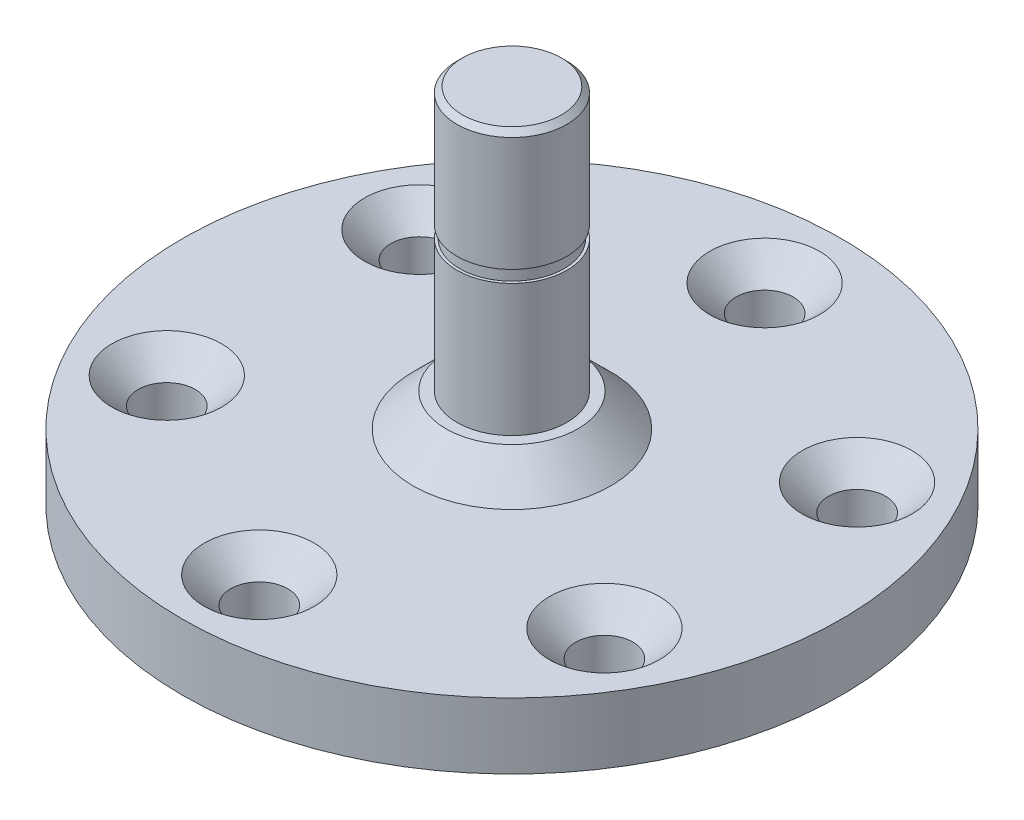
SolidWorks part; units mm, degrees
material "AISI 304"
ref_plane "前视基准面" through (0, 0, 0) normal (0, 0, 1) x (1, 0, 0)
ref_plane "上视基准面" through (0, 0, 0) normal (0, 1, 0) x (1, 0, 0)
ref_plane "右视基准面" through (0, 0, 0) normal (1, 0, 0) x (0, 0, -1)
sketch "草图1" plane through (0, 0, 0) normal (0, 1, 0) x (1, 0, 0)
  circle A0 centre (0, 0) radius 30
  dimension "D1" = 60
extrude "凸台-拉伸1" add sketch "草图1" along normal blind 6
sketch "草图2" plane through (0, 6, 0) normal (0, 1, 0) x (1, 0, 0)
  circle A0 centre (0, 0) radius 6
  dimension "D1" = 12
extrude "凸台-拉伸2" add sketch "草图2" along normal blind 3
sketch "草图3" plane through (0, 9, 0) normal (0, 1, 0) x (1, 0, 0)
  circle A0 centre (0, 0) radius 5
  dimension "D1" = 10
extrude "凸台-拉伸3" add sketch "草图3" along normal blind 24
sketch "草图4" plane through (0, 33, 0) normal (0, 1, 0) x (1, 0, 0)
  circle A0 centre (0, 0) radius 4.75
  dimension "D1" = 9.5
extrude "切除-拉伸1" cut sketch "草图4" along normal blind 1.1 from offset 12 flip side to cut offset against normal yes
sketch "草图5" plane through (0, 6, 0) normal (0, 1, 0) x (1, 0, 0)
  circle A0 centre (0, 0) radius 23 construction
  circle A1 centre (0, 23) radius 2.6
  circle A2 centre (19.9186, 11.5) radius 2.6
  circle A3 centre (19.9186, -11.5) radius 2.6
  circle A4 centre (0, -23) radius 2.6
  circle A5 centre (-19.9186, -11.5) radius 2.6
  circle A6 centre (-19.9186, 11.5) radius 2.6
  point P17 (0, 0)
  dimension "D1" = 46
  dimension "D2" = 5.2
  dimension "D3" = 6
extrude "切除-拉伸2" cut sketch "草图5" against normal through all
chamfer "倒角1" distance 3 angle 45 1 edges at (0, 6, 6)
chamfer "倒角2" distance 0.5 angle 45 1 edges at (0, 33, 5)
sketch "草图6" plane through (0, 0, 0) normal (0, -1, 0) x (1, 0, 0)
  circle A0 centre (0, 0) radius 13
  dimension "D1" = 26
extrude "切除-拉伸3" cut sketch "草图6" against normal blind 1.2
sketch "草图7" plane through (0, 0, 0) normal (1, 0, 0) x (0, 0, -1)
  line L0 (-23, 6) -> (-23, -1.4705) construction
  line L1 (-20.4, 6) -> (-25.6, 6) construction
  line L2 (-28, 6) -> (-23, 6)
  line L3 (30, 6) -> (-30, 6) construction
  line L4 (-23, 6) -> (-23, 1.9)
  line L5 (-23, 1.9) -> (-23.9, 1.9)
  line L6 (-23.9, 1.9) -> (-28, 6)
  dimension "D1" = 4.1
  dimension "D2" = 5
  dimension "D3" = 45
revolve "切除-旋转1" cut sketch "草图7" angle 360 about L0
pattern_circular "阵列(圆周)1" count 6 over 360 about axis through (0, 33, 0) along (0, -1, 0) of "切除-旋转1"
